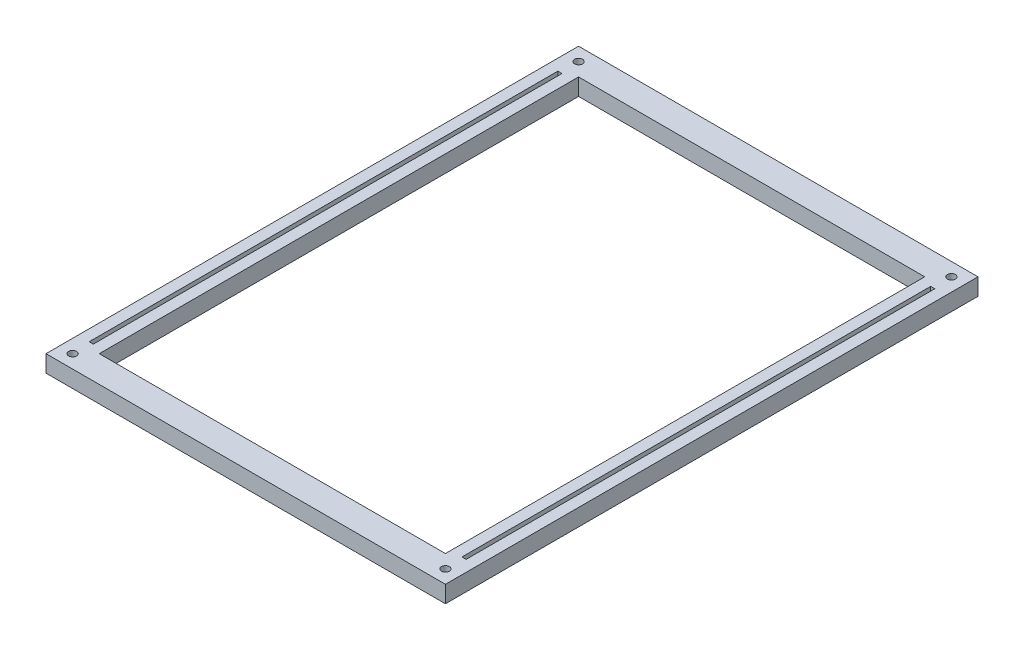
SolidWorks part; units mm, degrees
ref_plane "Front Plane" through (0, 0, 0) normal (0, 0, 1) x (1, 0, 0)
ref_plane "Top Plane" through (0, 0, 0) normal (0, 1, 0) x (1, 0, 0)
ref_plane "Right Plane" through (0, 0, 0) normal (1, 0, 0) x (0, 0, -1)
sketch "Sketch1" plane through (0, 0, 0) normal (0, 1, 0) x (1, 0, 0)
  line L0 (-65, 90) -> (65, 90)
  line L5 (-75, -100) -> (75, -100)
  line L6 (-75, -100) -> (-75, 100)
  line L7 (-75, 100) -> (75, 100)
  line L8 (75, -100) -> (75, 100)
  line L9 (-75, -100) -> (75, 100) construction
  line L10 (-75, 100) -> (75, -100) construction
  line L11 (65, -90) -> (65, 90)
  line L12 (-65, -90) -> (65, -90)
  line L13 (-65, -90) -> (-65, 90)
  line L32 (0, 100) -> (0, -100) construction
  point P0 (0, 0)
  dimension "D2" = 150
  dimension "D3" = 200
  dimension "D1" = 10
extrude "MainBody" add sketch "Sketch1" along normal mid plane 6.35
sketch "Sketch2" plane through (0, 3.175, 0) normal (0, 1, 0) x (1, 0, 0)
  line L0 (-65, 88) -> (-75, 88) construction
  line L4 (-65, 90) -> (-65, -90) construction
  line L10 (-75, 100) -> (-75, -100) construction
  line L11 (-70, 88) -> (-70, 0) construction
  line L12 (65, 90) -> (-65, 90) construction
  line L13 (75, 100) -> (-75, 100) construction
  line L18 (0, 0) -> (0, 100) construction
  line L27 (-70.7779, -88) -> (-69.2221, -88)
  line L28 (-70.7779, -88) -> (-70.7779, 88)
  line L29 (-70.7779, 88) -> (-69.2221, 88)
  line L30 (-69.2221, -88) -> (-69.2221, 88)
  line L31 (-70.7779, -88) -> (-69.2221, 88) construction
  line L32 (-70.7779, 88) -> (-69.2221, -88) construction
  dimension "D1" = 2
  dimension "D2" = 1.5557
extrude "SheetLock" cut sketch "Sketch2" against normal up to next
mirror "Mirror1" about plane through (0, 0, 0) normal (1, 0, 0) of "SheetLock"
sketch "Sketch3" plane through (0, 3.175, 0) normal (0, 1, 0) x (1, 0, 0)
  line L0 (0, 100) -> (0, -100) construction
  line L1 (75, 100) -> (-75, 100) construction
  line L2 (-75, -100) -> (75, -100) construction
  line L3 (-75, 0) -> (75, 0) construction
  line L4 (-75, 100) -> (-75, -100) construction
  line L5 (75, -100) -> (75, 100) construction
  line L6 (-65, 90) -> (-65, 100) construction
  line L7 (-65, 90) -> (-75, 90) construction
  circle A0 centre (-70, 95) radius 1.5
  circle A1 centre (70, 95) radius 1.5
  circle A2 centre (70, -95) radius 1.5
  circle A3 centre (-70, -95) radius 1.5
  point P19 (-65, 95)
  point P20 (-70, 90)
  dimension "D1" = 3
extrude "SupportHoles" cut sketch "Sketch3" against normal up to next
equation "\"SheetLockLengthOffset\"=2"
equation "\"SheetThickness\"=0.79375"
equation "\"SheetThicknessTolerance\"= 0.015in"
equation "\"LowerBasketWidth\"=150"
equation "\"D2@Sketch1\"=\"LowerBasketWidth\""
equation "\"LowerBasketLength\"=200"
equation "\"D3@Sketch1\"=\"LowerBasketLength\""
equation "\"SupportHoleDiameter\"=3"
equation "\"D1@Sketch3\"=\"SupportHoleDiameter\""
equation "\"InnerGapOffset\"=10"
equation "\"D1@Sketch1\"=\"InnerGapOffset\""
equation "\"D1@Sketch2\"=\"SheetLockLengthOffset\""
equation "\"D2@Sketch2\"=\"SheetThickness\" + \"SheetThicknessTolerance\"*2"
